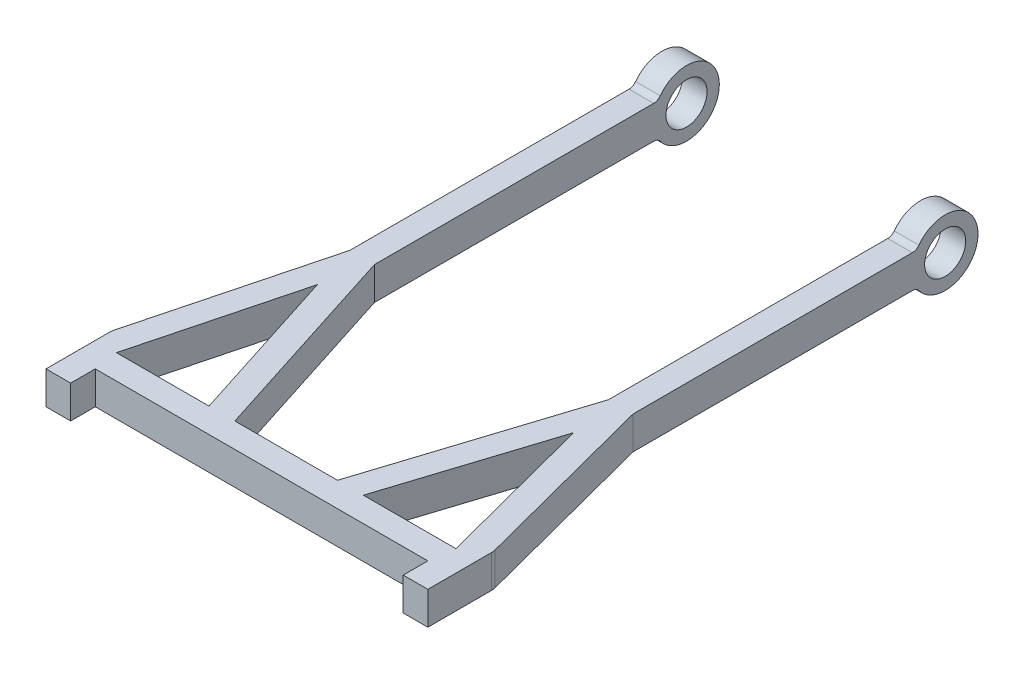
SolidWorks part; units mm, degrees
ref_plane "Front Plane" through (0, 0, 0) normal (0, 0, 1) x (1, 0, 0)
ref_plane "Top Plane" through (0, 0, 0) normal (0, 1, 0) x (1, 0, 0)
ref_plane "Right Plane" through (0, 0, 0) normal (1, 0, 0) x (0, 0, -1)
sketch "Sketch1" plane through (0, 0, 0) normal (0, 1, 0) x (1, 0, 0)
  line L6 (-4.6999, 0.75) -> (-7.8046, 10.4522)
  line L7 (-10.3357, 0.75) -> (-4.6999, 0.75)
  line L9 (-10.125, -0.75) -> (0, -0.75)
  line L10 (0, 0.75) -> (0, -0.75)
  line L11 (-3.125, 0.75) -> (-7.125, 13.25)
  line L12 (-7.8046, 10.4522) -> (-10.3357, 0.75)
  line L13 (-11.625, -0.75) -> (-11.625, 1.6217)
  line L14 (-11.5926, 1.8741) -> (-8.625, 13.25)
  line L15 (-3.125, 0.75) -> (0, 0.75)
  line L16 (0, 0.75) -> (0, 5.5445) construction
  line L17 (-8.625, 30.25) -> (-7.125, 30.25)
  line L18 (-8.625, 30.25) -> (-8.625, 13.25)
  line L19 (-8.625, 13.25) -> (-7.125, 13.25) construction
  line L20 (-7.125, 30.25) -> (-7.125, 13.25)
  line L21 (-11.625, -0.75) -> (-10.125, -0.75) construction
  line L22 (-11.625, -2.25) -> (-10.125, -2.25)
  line L23 (-11.625, -2.25) -> (-11.625, -0.75)
  line L25 (-10.125, -2.25) -> (-10.125, -0.75)
  arc A0 (-11.625, 1.6217) -> (-11.5926, 1.8741) centre (-10.625, 1.6217) cw
  point P17 (0, 0)
  point P20 (-11.625, 1.75)
  dimension "D13" = 1
  dimension "D1" = 1.5
  dimension "D2" = 1.5
  dimension "D3" = 1.5
  dimension "D4" = 1.5
  dimension "D5" = 6.25
  dimension "D6" = 14.25
  dimension "D7" = 23.25
  dimension "D8" = 2.5
  dimension "D9" = 14
  dimension "D10" = 31
  dimension "D11" = 1.5
  dimension "D12" = 1.5
extrude "Boss-Extrude1" add sketch "Sketch1" along normal mid plane 2
mirror "Mirror1" about plane through (0, 0, 0) normal (1, 0, 0) of "Boss-Extrude1"
sketch "Sketch2" plane through (0, 0, 0) normal (1, 0, 0) x (0, 0, -1)
  line L0 (30.25, 1) -> (30.25, -1)
  line L1 (0, 0) -> (10.9707, 0) construction
  line L2 (30.25, 1) -> (30.25, -1) construction
  arc A0 (30.65, -1.2) -> (30.65, 1.2) centre (32.25, 0) ccw
  arc A1 (30.25, 1) -> (30.65, 1.2) centre (30.25, 1.5) ccw
  arc A2 (30.25, -1) -> (30.65, -1.2) centre (30.25, -1.5) cw
  arc A3 (30.65, 1.2) -> (30.65, -1.2) centre (32.25, 0) ccw construction
  point P1 (29.9805, 1.5954)
  point P7 (30.25, 0)
  point P12 (31.9922, 0)
  point P13 (29.4418, -0.7805)
  point P14 (31.0225, 1.1118)
  point P15 (29.4236, 1.1118)
  point P16 (29.9414, 1.339)
  point P19 (29.693, 1.3574)
  point P20 (0, 0)
  point P21 (0, 0)
  point P23 (29.7262, 1.3217)
  point P24 (29.7212, 1.2893)
  point P25 (29.6339, 1.2377)
  dimension "D1" = 4
  dimension "D2" = 0.5
extrude "Boss-Extrude2" add sketch "Sketch2" along normal up to surface (8.625 mm away) from surface up to face at (8.625, 0, -21.75) starting at face at (7.125, 0, -21.75)
extrude "Boss-Extrude3" add sketch "Sketch2<2>" along normal up to surface (-7.125 mm away) from surface up to face at (-7.125, 0, -21.75) starting at face at (-8.625, 0, -21.75)
sketch "Sketch2<2>" plane through (0, 0, 0) normal (1, 0, 0) x (0, 0, -1) same geometry as "Sketch2"
sketch "Sketch3" plane through (0, 0, 0) normal (1, 0, 0) x (0, 0, -1)
  circle A0 centre (32.25, 0) radius 1.25
  arc A1 (30.65, -1.2) -> (30.65, 1.2) centre (32.25, 0) ccw construction
  dimension "D1" = 2.5
extrude "Cut-Extrude1" cut sketch "Sketch3" against normal through all both and the other way through all
equation "\"univ\" = 6.25"
equation "\"D5@Sketch1\"=\"univ\""
equation "\"D6@Sketch1\"=\"univ\"+8"
equation "\"D7@Sketch1\"=\"univ\"+17"
